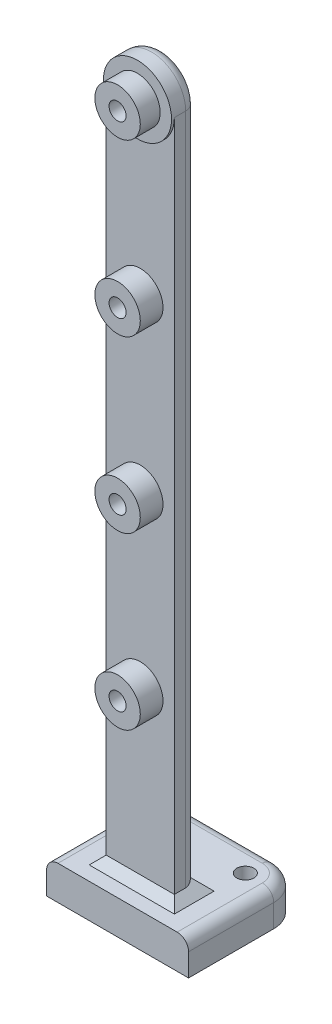
SolidWorks part; units mm, degrees
ref_plane "前视基准面" through (0, 0, 0) normal (0, 0, 1) x (1, 0, 0)
ref_plane "上视基准面" through (0, 0, 0) normal (0, 1, 0) x (1, 0, 0)
ref_plane "右视基准面" through (0, 0, 0) normal (1, 0, 0) x (0, 0, -1)
sketch "草图1" plane through (0, 0, 0) normal (0, 0, 1) x (1, 0, 0)
  line L0 (0, 60) -> (0, -60) construction
  line L1 (6, 60) -> (6, -60)
  line L2 (-6, 60) -> (-6, -60)
  arc A0 (6, 60) -> (-6, 60) centre (0, 60) ccw
  arc A1 (-6, -60) -> (6, -60) centre (0, -60) ccw
  circle A2 centre (0, 60) radius 1.5
  circle A3 centre (0, 0) radius 1.5
  circle A4 centre (0, 30) radius 1.5
  circle A5 centre (0, -30) radius 1.5
  circle A6 centre (0, 60) radius 4
  circle A7 centre (0, 30) radius 4
  circle A8 centre (0, 0) radius 4
  circle A9 centre (0, -30) radius 4
  circle A10 centre (0, 60) radius 6
  point P3 (0, 0)
  dimension "D3" = 6
  dimension "D4" = 30
  dimension "D1" = 120
  dimension "D2" = 0
  dimension "D5" = 30
extrude "凸台-拉伸1" add sketch "草图1" along normal blind 4 contours L2 A1 L1 A0 A6 A7 A8 A9 | A10 | A2 region at (0, -5.2636, 0)
extrude "凸台-拉伸3" add sketch "草图1<4>" along normal blind 8 contours L0 A7 A4 | A7 L0 A4 | A2 A6 | A8 L0 A3 | L0 A8 A3 | A9 L0 A5 | L0 A9 A5 region at (-2.7484, 62.7484, 0) region at (1.8713, -30, 0) region at (-1.8713, -30, 0) region at (1.8713, 0, 0) region at (-1.8713, 0, 0) region at (1.8713, 30, 0) region at (-1.8713, 30, 0)
sketch "草图1<4>" plane through (0, 0, 0) normal (0, 0, 1) x (1, 0, 0) same geometry as "草图1"
extrude "凸台-拉伸4" add sketch "草图1<5>" along normal blind 4.5 contours A6 A10 A0 region at (0, 54.1697, 0)
sketch "草图1<5>" plane through (0, 0, 0) normal (0, 0, 1) x (1, 0, 0) same geometry as "草图1"
ref_plane "基准面4" through (0, 0, 8) normal (0, 0, 1) x (1, 0, 0)
sketch "草图2" plane through (0, 0, 8) normal (0, 0, 1) x (1, 0, 0)
  line L0 (-6, 60) -> (-6, -60) construction
  line L1 (-12.5, -60) -> (12.5, -60)
  line L2 (-12.5, -60) -> (-12.5, -66)
  line L3 (-12.5, -66) -> (12.5, -66)
  line L4 (12.5, -60) -> (12.5, -66)
  arc A0 (-6, -60) -> (6, -60) centre (0, -60) ccw construction
  point P9 (0, -66)
  dimension "D1" = 6.5
  dimension "D2" = 6
  dimension "D3" = 25
  dimension "D4" = 6
extrude "凸台-拉伸5" add sketch "草图2" against normal blind 20
chamfer "倒角1" distance 1.5 angle 45 4 edges at (0, -60, 0) (-6, -60, 2) (0, -60, 4) (6, -60, 2)
fillet "圆角1" radius 2 3 edges at (-6, 0.75, 0) (0, 66, 0) (6, 0.75, 0)
fillet "圆角2" radius 5 2 edges at (-12.5, -63, -12) (12.5, -63, -12)
fillet "圆角4" radius 2 5 edges at (-11.0355, -60, -10.5355) (-12.5, -60, 0.5) (0, -60, -12) (11.0355, -60, -10.5355) (12.5, -60, 0.5)
sketch "草图3" plane through (0, -60, 0) normal (0, 1, 0) x (1, 0, 0)
  line L0 (-7.5, 12) -> (7.5, 12) construction
  line L1 (-12.5, -8) -> (-12.5, 7) construction
  line L3 (12.5, 7) -> (12.5, -8) construction
  circle A0 centre (-7.5, 7) radius 1.5
  circle A1 centre (7.5, 7) radius 1.5
  dimension "D1" = 5
  dimension "D2" = 5
  dimension "D3" = 5
  dimension "D4" = 5
  dimension "D5" = 15
extrude "切除-拉伸1" cut sketch "草图3" against normal blind 20
